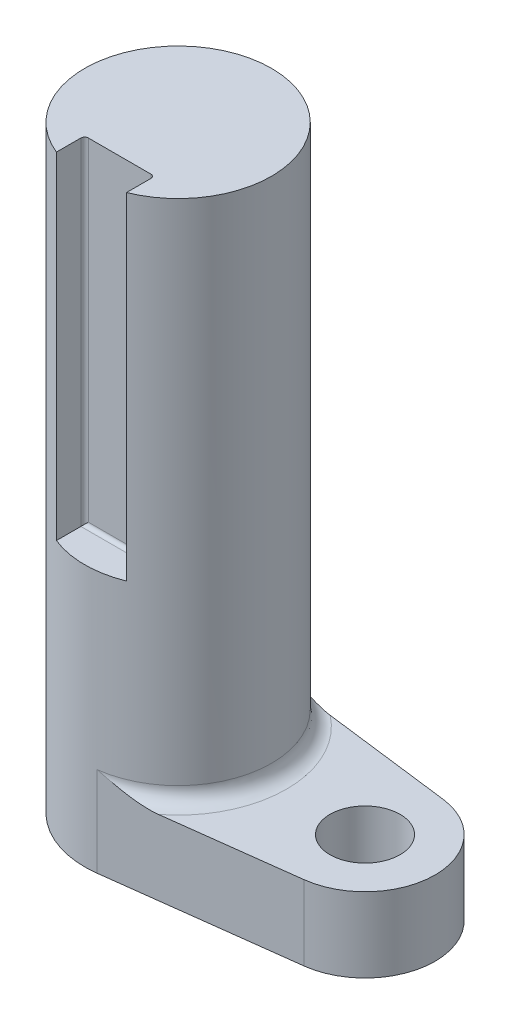
SolidWorks part; units mm, degrees
ref_plane "Front Plane" through (0, 0, 0) normal (0, 0, 1) x (1, 0, 0)
ref_plane "Top Plane" through (0, 0, 0) normal (0, 1, 0) x (1, 0, 0)
ref_plane "Right Plane" through (0, 0, 0) normal (1, 0, 0) x (0, 0, -1)
sketch "Sketch1" plane through (0, 0, 0) normal (0, 1, 0) x (1, 0, 0)
  circle A0 centre (0, 0) radius 3.175
  dimension "D1" = 6.35
extrude "Boss-Extrude1" add sketch "Sketch1" along normal blind 17.78
cosmetic thread "Cosmetic Thread2" parameters "D1"=7.62, "D2"=5.268
sketch "Sketch2" plane through (0, 0, 0) normal (0, -1, 0) x (1, 0, 0)
  line L0 (-10.6761, 0) -> (14.4716, 0) construction
  line L1 (0.3969, 3.1501) -> (6.6477, 2.3626)
  line L2 (6.6477, -2.3626) -> (0.3969, -3.1501)
  circle A0 centre (6.35, 0) radius 1.1906
  circle A1 centre (0, 0) radius 3.175 construction
  arc A2 (6.6477, 2.3626) -> (6.6477, -2.3626) centre (6.35, 0) cw
  point P5 (6.7469, 1.5264)
  point P11 (2.9629, -2.9751)
  point P13 (0, 0)
  circle M4 centre (0, 0) radius 3.175
  dimension "D2" = 2.3813
  dimension "D3" = 2.3813
  dimension "D1" = 6.35
extrude "Boss-Extrude2" add sketch "Sketch2" along normal blind 2.54 contours L0 M4 | L0 A0 A2 L1 M4 | L0 L2 A2 A0 M4 | L0 M4 region at (0, 0, 1.3475) region at (0, 0, -1.3475) region at (5.108, 0, 1.4695) region at (5.108, 0, -1.4695)
fillet "Fillet1" radius 0.508 1 edges at (3.175, 0, 0)
sketch "Sketch3" plane through (0, 0, 0) normal (0, 1, 0) x (1, 0, 0)
  line L0 (0, -5.1656) -> (0, 6.1347) construction
  line L1 (-6.2309, 0) -> (11.0317, 0) construction
  line L3 (-1.1906, -4.3637) -> (1.1906, -4.3637)
  line L4 (-1.1906, -4.3637) -> (-1.1906, -1.9863)
  line L5 (-1.1906, -1.9863) -> (1.1906, -1.9863)
  line L6 (1.1906, -4.3637) -> (1.1906, -1.9863)
  line L7 (-1.1906, -4.3637) -> (1.1906, -1.9863) construction
  line L8 (-1.1906, -1.9863) -> (1.1906, -4.3637) construction
  arc A0 (0.3969, 3.1501) -> (0.3969, -3.1501) centre (0, 0) ccw construction
  point P5 (0, -3.175)
  point P10 (0, -3.175)
  dimension "D1" = 1.1887
  dimension "D2" = 2.3813
extrude "Cut-Extrude2" cut sketch "Sketch3" along normal blind 12.7 from offset 6.35
fillet "Fillet2" radius 0.127 3 edges at (-1.1906, 12.065, 1.9863) (1.1906, 12.065, 1.9863) (0, 6.35, 1.9863)
